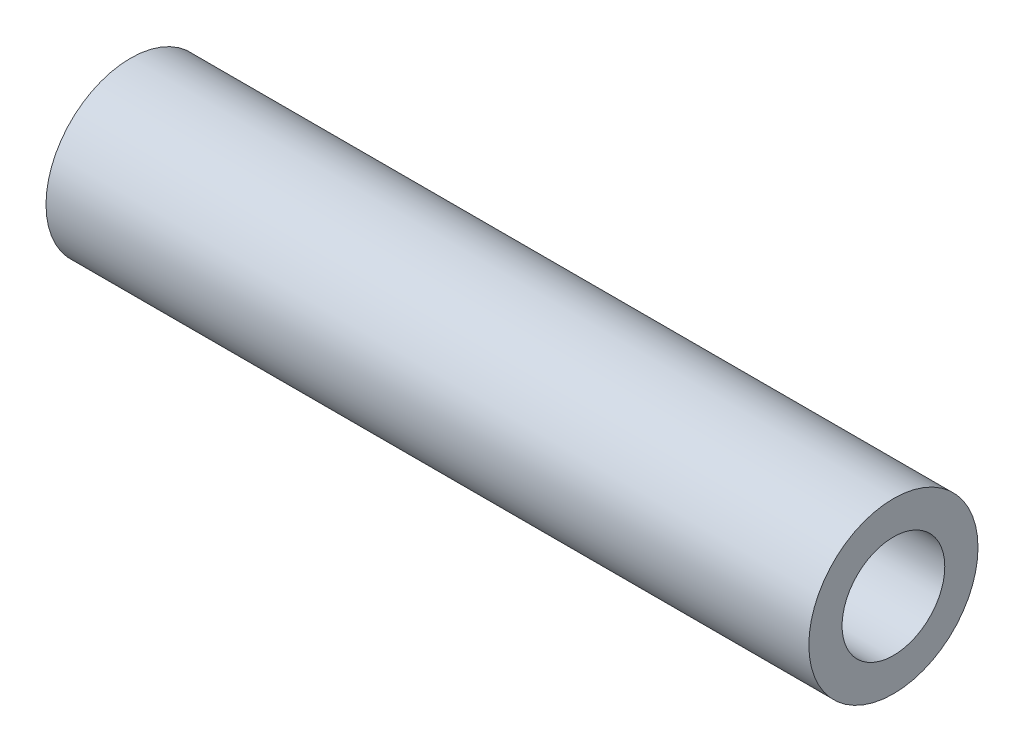
SolidWorks part; units mm, degrees
material "Epoxy, Unfilled"
ref_plane "Ebene vorne" through (0, 0, 0) normal (0, 0, 1) x (1, 0, 0)
ref_plane "Ebene oben" through (0, 0, 0) normal (0, 1, 0) x (1, 0, 0)
ref_plane "Ebene rechts" through (0, 0, 0) normal (1, 0, 0) x (0, 0, -1)
sketch "Sketch1" plane through (0, 0, 0) normal (1, 0, 0) x (0, 0, -1)
  circle A0 centre (0, 0) radius 47.675
  circle A1 centre (0, 0) radius 28.95
  dimension "D1" = 95.35
  dimension "D2" = 57.9
extrude "Boss-Extrude1" add sketch "Sketch1" along normal blind 430
